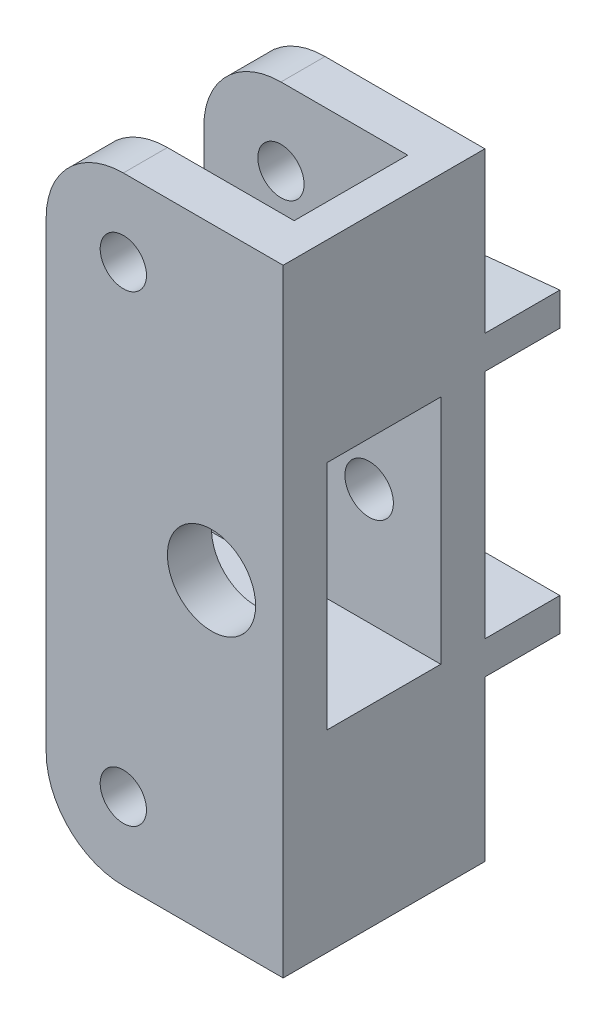
SolidWorks part; units mm, degrees
ref_plane "前视基准面" through (0, 0, 0) normal (0, 0, 1) x (1, 0, 0)
ref_plane "上视基准面" through (0, 0, 0) normal (0, 1, 0) x (1, 0, 0)
ref_plane "右视基准面" through (0, 0, 0) normal (1, 0, 0) x (0, 0, -1)
sketch "草图1" plane through (0, 0, 0) normal (0, 0, 1) x (1, 0, 0)
  line L0 (-612.4365, 0) -> (30009.3904, 0) construction
  line L1 (-611.4109, 10) -> (30010.416, 10) construction
  line L2 (-607.9921, -10) -> (30013.8348, -10) construction
  line L3 (0, -612.4365) -> (0, 30009.3904) construction
  line L4 (-10, -612.4365) -> (-10, 30009.3904) construction
  line L5 (10, -614.6741) -> (10, 30007.1528) construction
  line L6 (-37, -1047.5802) -> (-37, 48952.4198) construction
  line L7 (-1052.765, 15) -> (48947.235, 15) construction
  line L8 (-50, 21) -> (-50, -21)
  line L9 (-50, 10.5) -> (-28.5, 10.5)
  line L11 (-11, -31.9293) -> (-11, 31.9293) construction
  line L12 (-31, -1000) -> (-31, 49000) construction
  line L13 (-25, -1048.411) -> (-25, 48951.589) construction
  line L14 (-43, 28) -> (-28.5, 28)
  line L15 (-43, 12.1) -> (-50, 12.1)
  line L16 (-34.5021, 18.3549) -> (-31.5, 28)
  line L17 (-28.5, 28) -> (-28.5, 10.5)
  line L18 (-28.5, 10.5) -> (-28.5, -10.5)
  line L19 (-28.5, -28) -> (-28.5, -10.5)
  line L20 (-34.5021, -18.3549) -> (-31.5, -28)
  line L21 (-43, -12.1) -> (-50, -12.1)
  line L22 (-43, -28) -> (-28.5, -28)
  line L23 (-50, -10.5) -> (-28.5, -10.5)
  line L26 (-42.118, 12.1438) -> (-28.5, 13.5)
  line L27 (-42.118, -12.1438) -> (-28.5, -13.5)
  circle A0 centre (-43, 21) radius 6 construction
  circle A1 centre (-43, 21) radius 7
  circle A2 centre (-43, 21) radius 2.1
  arc A3 (-43, 12.1) -> (-34.5021, 18.3549) centre (-43, 21) ccw
  circle A4 centre (-35, 0) radius 2.2
  circle A5 centre (-43, -21) radius 6 construction
  arc A6 (-43, -12.1) -> (-34.5021, -18.3549) centre (-43, -21) cw
  circle A7 centre (-43, -21) radius 2.1
  circle A12 centre (-43, -21) radius 7
  circle A13 centre (-35, 0) radius 4
  point P50 (-28.5, 0)
  point P56 (-50, 0)
  dimension "D5" = 12
  dimension "D6" = 14
  dimension "D7" = 4.2
  dimension "D9" = 5
  dimension "D10" = 1.6
  dimension "D11" = 10.5
  dimension "D12" = 3
  dimension "D8" = 12
  dimension "D18" = 4.4
  dimension "D19" = 3.5
  dimension "D25" = 40
  dimension "D15" = 8
  dimension "D1" = 20
  dimension "D2" = 10
  dimension "D3" = 20
  dimension "D4" = 10
  dimension "D13" = 8.9
  dimension "D14" = 6
  dimension "D16" = 21
  dimension "D17" = 15
  dimension "D22" = 3
  dimension "D23" = 18.5
  dimension "D24" = 1
extrude "凸台-拉伸1" add sketch "草图1" along normal blind 4 contours L15 A3 L16 L14 A1 L8 | A1 A2 | A3 L15 L8 L9 L17 L14 L16 | L8 L23 L18 L9 | L21 A6 L20 L22 L19 L23 L8 | L8 A12 L22 L20 A6 L21 | A12 A7 | A3 L26 L17 L14 L16 | L27 A6 L20 L22 L19 region at (-43, 13.7561, 0) region at (-47.8097, 25.8097, 0) region at (-37.9015, 11.5818, 0) region at (-39.7824, 0, 0) region at (-31.7873, 19.0677, 0) region at (-37.9015, -11.5818, 0) region at (-46.5, -12.3439, 0) region at (-43, -14.198, 0) region at (-31.7873, -19.0677, 0)
extrude "凸台-拉伸2" add sketch "草图1<5>" against normal blind 10.3 contours A3 L15 L8 L9 L17 L14 L16 | L21 A6 L20 L22 L19 L23 L8 | A3 L26 L17 L14 L16 | L27 A6 L20 L22 L19 region at (-37.9015, 11.5818, 0) region at (-31.7873, 19.0677, 0) region at (-37.9015, -11.5818, 0) region at (-31.7873, -19.0677, 0)
sketch "草图1<5>" plane through (0, 0, 0) normal (0, 0, 1) x (1, 0, 0) same geometry as "草图1"
extrude "凸台-拉伸3" add sketch "草图1<6>" against normal blind 4 from vertex contours L15 A3 L16 L14 A1 L8 | A3 L15 L8 L9 L17 L14 L16 | A1 A2 | L8 L23 L18 L9 | A4 | L21 A6 L20 L22 L19 L23 L8 | L8 A12 L22 L20 A6 L21 | A12 A7 | A3 L26 L17 L14 L16 | L27 A6 L20 L22 L19 region at (-43, 13.7561, 0) region at (-47.8097, 25.8097, 0) region at (-37.9015, 11.5818, 0) region at (-39.7824, 0, 0) region at (-31.7873, 19.0677, 0) region at (-37.9015, -11.5818, 0) region at (-46.5, -12.3439, 0) region at (-43, -14.198, 0) region at (-31.7873, -19.0677, 0) region at (-38.8869, 0, 0) starting at point (-28.5, 28, -10.3)
sketch "草图1<6>" plane through (0, 0, 0) normal (0, 0, 1) x (1, 0, 0) same geometry as "草图1"
extrude "凸台-拉伸4" add sketch "草图1<7>" against normal blind 6.8 from vertex contours A3 L15 L8 L9 L17 L26 | L21 A6 L27 L19 L23 L8 region at (-37.9015, 11.5818, 0) region at (-37.9015, -11.5818, 0) starting at point (-50, -21, -14.3)
sketch "草图1<7>" plane through (0, 0, 0) normal (0, 0, 1) x (1, 0, 0) same geometry as "草图1"
fillet "圆角1" radius 5 2 edges at (-50, 11.3, -21.1) (-50, -11.3, -21.1)
sketch "草图2" plane through (-28.5, 0, 0) normal (1, 0, 0) x (0, 0, -1)
  line L0 (14.3, -10.5) -> (10.3, -10.5)
  line L1 (10.3, -10.5) -> (10.3, 10.5)
  line L2 (10.3, 10.5) -> (14.3, 10.5)
  line L3 (14.3, 10.5) -> (14.3, -10.5)
extrude "凸台-拉伸5" [suppressed] add sketch "草图2" against normal blind 8 from vertex starting at point (-50, -10.5, -15)
sketch "草图3" [suppressed] plane through (0, 0, -11) normal (0, 0, 1) x (1, 0, 0)
  line L1 (-58, -10.5) -> (-58, 10.5) construction
  circle A0 centre (-53, 0) radius 2.2
  dimension "D1" = 4.4
  dimension "D2" = 5
extrude "切除-拉伸1" [suppressed] cut sketch "草图3" against normal through all
